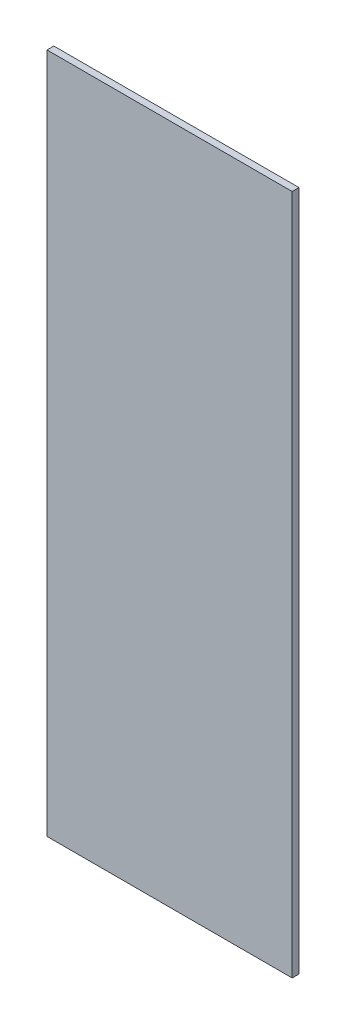
SolidWorks part; units mm, degrees
ref_plane "Front Plane" through (0, 0, 0) normal (1, 0, 0) x (0, 1, 0)
ref_plane "Top Plane" through (0, 0, 0) normal (0, 0, 1) x (0, 1, 0)
ref_plane "Right Plane" through (0, 0, 0) normal (0, 1, 0) x (-1, 0, 0)
sketch "Sketch1" plane through (0, 0, 0) normal (0, 0, 1) x (0, 1, 0)
  line L1 (-158.75, -57.15) -> (158.75, -57.15)
  line L2 (-158.75, -57.15) -> (-158.75, 57.15)
  line L3 (-158.75, 57.15) -> (158.75, 57.15)
  line L4 (158.75, -57.15) -> (158.75, 57.15)
  line L5 (-158.75, -57.15) -> (158.75, 57.15) construction
  line L6 (-158.75, 57.15) -> (158.75, -57.15) construction
  point P1 (0, 0)
  dimension "D1" = 317.5
  dimension "D2" = 114.3
extrude "Boss-Extrude1" add sketch "Sketch1" along normal blind 3.175
